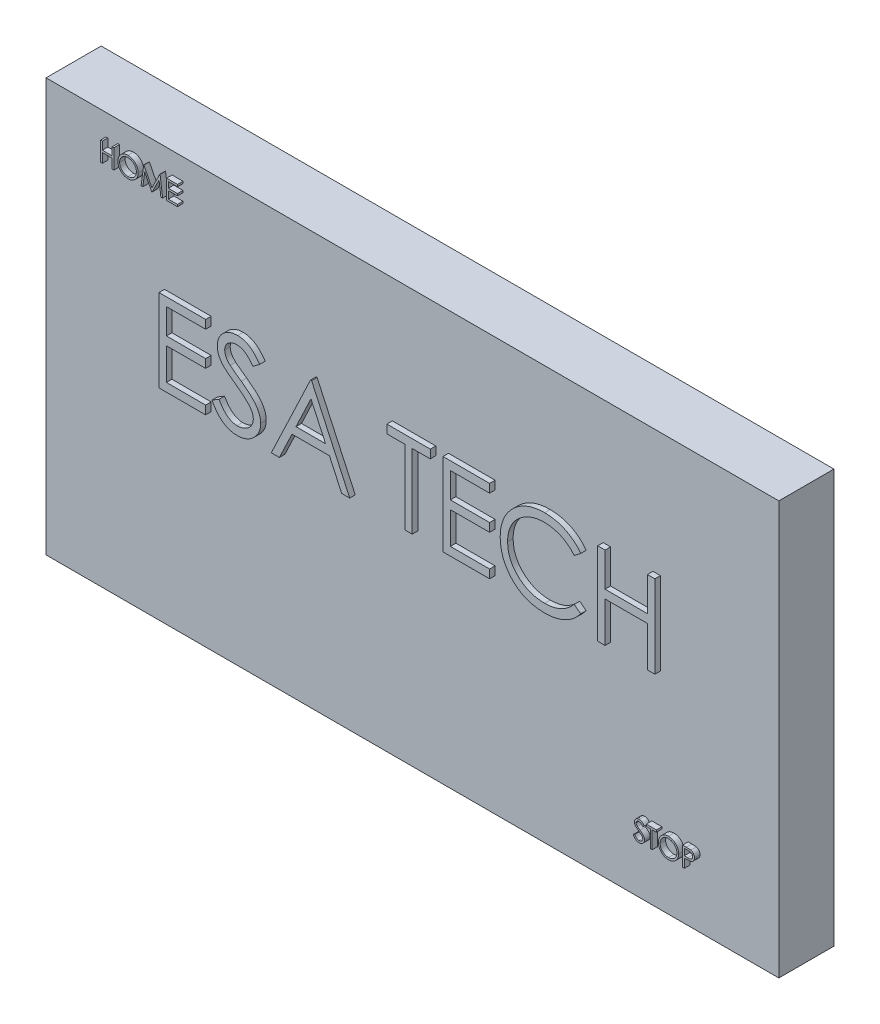
SolidWorks part; units mm, degrees
ref_plane "Front Plane" through (0, 0, 0) normal (0, 0, 1) x (1, 0, 0)
ref_plane "Top Plane" through (0, 0, 0) normal (0, 1, 0) x (1, 0, 0)
ref_plane "Right Plane" through (0, 0, 0) normal (1, 0, 0) x (0, 0, -1)
ref_plane "Plane1" through (0, 0, 10) normal (0, 0, 1) x (1, 0, 0)
sketch "Sketch1" plane through (0, 0, 10) normal (0, 0, 1) x (1, 0, 0)
  line L0 (66.5, 37.5) -> (-66.5, 37.5)
  line L1 (-66.5, 37.5) -> (-66.5, -37.5)
  line L2 (-66.5, -37.5) -> (66.5, -37.5)
  line L3 (66.5, -37.5) -> (66.5, 37.5)
extrude "Boss-Extrude1" add sketch "Sketch1" against normal blind 10
ref_plane "Plane2" through (0, 0, 13) normal (0, 0, -1) x (0, 1, 0)
sketch "Sketch2" plane through (0, 0, 13) normal (0, 0, -1) x (0, 1, 0)
  line L0 (11.9231, -27.9477) -> (12.8456, -26.7308)
  line L1 (3.6538, -34.1166) -> (2.8936, -35.3846)
  arc A0 (8.5156, -30.0721) -> (10.009, -32.0883) centre (34.1917, -12.6154) ccw
  spline S0 degree 3 poles (-0.3846, -30.8233) (-0.3828, -30.7354) (-0.3791, -30.5597) (-0.3616, -30.2964) (-0.3249, -30.0351) (-0.273, -29.7771) (-0.206, -29.5236) (-0.124, -29.2756) (-0.0267, -29.0332) (0.0861, -28.7967) (0.2147, -28.5673) (0.3586, -28.3469) (0.5159, -28.1364) (0.6848, -27.9356) (0.8638, -27.7433) (1.0538, -27.5611) (1.2539, -27.3901) (1.4634, -27.232) (1.681, -27.0864) (1.9094, -26.9577) (2.1476, -26.8461) (2.3915, -26.7477) (2.6418, -26.6696) (2.8957, -26.6115) (3.1522, -26.5662) (3.4127, -26.5437) (3.5873, -26.5402) (3.6749, -26.5385) knots 0 0 0 0 0.040239 0.080419 0.12065 0.160855 0.200779 0.240536 0.280292 0.320216 0.360325 0.400539 0.440561 0.480508 0.52052 0.560704 0.600885 0.640878 0.680723 0.720595 0.760706 0.800978 0.840861 0.880503 0.920116 0.959909 1 1 1 1
  spline S1 degree 3 poles (3.6749, -26.5385) (3.8144, -26.5452) (4.0934, -26.5588) (4.5063, -26.6299) (4.9044, -26.7529) (5.2878, -26.9125) (5.6551, -27.1073) (6.0058, -27.3308) (6.3374, -27.5804) (6.6472, -27.8548) (6.9432, -28.1442) (7.2272, -28.4464) (7.5011, -28.7582) (7.7664, -29.0775) (8.0219, -29.4047) (8.271, -29.7367) (8.4341, -29.9603) (8.5156, -30.0721) knots 0 0 0 0 0.067213 0.134445 0.201108 0.267468 0.334185 0.401073 0.467532 0.533824 0.600253 0.666833 0.733489 0.800114 0.866721 0.933348 1 1 1 1
  spline S2 degree 3 poles (10.009, -32.0883) (10.0675, -32.1477) (10.1844, -32.2663) (10.3662, -32.4375) (10.5587, -32.5955) (10.7619, -32.7375) (10.9777, -32.8593) (11.2075, -32.9565) (11.4492, -33.021) (11.6959, -33.0711) (11.8632, -33.075) (11.9471, -33.0769) knots 0 0 0 0 0.111361 0.222694 0.333843 0.444007 0.553828 0.664575 0.776591 0.888 1 1 1 1
  spline S3 degree 3 poles (11.9471, -33.0769) (12.0188, -33.0728) (12.1616, -33.0647) (12.3744, -33.0345) (12.5811, -32.9725) (12.7782, -32.8835) (12.9626, -32.77) (13.1312, -32.6343) (13.2837, -32.4803) (13.4211, -32.3123) (13.541, -32.1309) (13.6399, -31.9374) (13.7192, -31.7352) (13.7803, -31.527) (13.8207, -31.3131) (13.8388, -31.0956) (13.8437, -30.9501) (13.8462, -30.8774) knots 0 0 0 0 0.066366 0.132192 0.198089 0.265068 0.331533 0.397751 0.464609 0.531455 0.598099 0.66518 0.731934 0.798505 0.865495 0.932744 1 1 1 1
  spline S4 degree 3 poles (13.8462, -30.8774) (13.8425, -30.7829) (13.8352, -30.5941) (13.7967, -30.3139) (13.7254, -30.0416) (13.6261, -29.7791) (13.4983, -29.5287) (13.3461, -29.2923) (13.1712, -29.0731) (12.9803, -28.8684) (12.7821, -28.6704) (12.5757, -28.4802) (12.362, -28.2981) (12.1444, -28.1206) (11.9969, -28.0053) (11.9231, -27.9477) knots 0 0 0 0 0.077694 0.15521 0.231898 0.308459 0.38546 0.462477 0.539061 0.615599 0.69236 0.769264 0.846171 0.923073 1 1 1 1
  spline S5 degree 3 poles (12.8456, -26.7308) (12.9346, -26.7957) (13.1125, -26.9255) (13.3733, -27.1281) (13.6268, -27.3394) (13.8742, -27.558) (14.1129, -27.7868) (14.3397, -28.0274) (14.5511, -28.2803) (14.7436, -28.5467) (14.9107, -28.83) (15.055, -29.1268) (15.176, -29.4343) (15.2716, -29.7494) (15.3397, -30.0706) (15.3732, -30.3978) (15.3808, -30.6171) (15.3846, -30.7272) knots 0 0 0 0 0.066899 0.133692 0.200414 0.267147 0.334091 0.40104 0.467733 0.534051 0.600333 0.667098 0.734185 0.800673 0.86681 0.933166 1 1 1 1
  spline S6 degree 3 poles (15.3846, -30.7272) (15.3797, -30.8534) (15.3698, -31.1049) (15.3257, -31.4802) (15.2376, -31.8482) (15.1135, -32.2065) (14.958, -32.553) (14.7669, -32.8811) (14.5469, -33.1905) (14.2928, -33.4725) (14.0048, -33.718) (13.6951, -33.9355) (13.3607, -34.1145) (13.0074, -34.2527) (12.6414, -34.3528) (12.2648, -34.4103) (12.011, -34.4188) (11.884, -34.4231) knots 0 0 0 0 0.066708 0.132979 0.199237 0.266167 0.33303 0.399559 0.466405 0.533284 0.599492 0.665897 0.732872 0.799317 0.865884 0.932947 1 1 1 1
  spline S7 degree 3 poles (11.884, -34.4231) (11.8204, -34.4218) (11.6935, -34.4193) (11.5039, -34.4063) (11.3162, -34.3798) (11.1301, -34.3439) (10.9458, -34.2968) (10.7644, -34.2373) (10.585, -34.1702) (10.4091, -34.0939) (10.2376, -34.0085) (10.0711, -33.9137) (9.9104, -33.8096) (9.7538, -33.6993) (9.6515, -33.6229) (9.6004, -33.5847) knots 0 0 0 0 0.076926 0.153469 0.229724 0.305984 0.382514 0.459603 0.536847 0.614055 0.691256 0.768476 0.845618 0.922773 1 1 1 1
  spline S8 degree 3 poles (9.6004, -33.5847) (9.5262, -33.5219) (9.378, -33.3966) (9.1741, -33.1886) (8.9816, -32.9707) (8.7931, -32.749) (8.6088, -32.5235) (8.4282, -32.2952) (8.25, -32.0649) (8.0738, -31.8331) (7.8999, -31.5997) (7.7291, -31.3638) (7.6164, -31.2058) (7.5601, -31.1268) knots 0 0 0 0 0.09103 0.18176 0.272565 0.363469 0.454414 0.545345 0.636277 0.727213 0.818142 0.909068 1 1 1 1
  spline S9 degree 3 poles (7.5601, -31.1268) (7.4959, -31.0377) (7.3675, -30.8595) (7.173, -30.5936) (6.9749, -30.3304) (6.7708, -30.0717) (6.5621, -29.8167) (6.3506, -29.564) (6.131, -29.3184) (5.9047, -29.079) (5.6727, -28.8453) (5.4275, -28.6254) (5.2547, -28.4902) (5.1683, -28.4225) knots 0 0 0 0 0.090938 0.181862 0.272772 0.363703 0.45466 0.545612 0.636551 0.727489 0.818361 0.909111 1 1 1 1
  spline S10 degree 3 poles (5.1683, -28.4225) (5.1194, -28.3889) (5.0217, -28.3218) (4.8724, -28.2255) (4.7177, -28.1389) (4.5576, -28.0641) (4.3931, -28.0003) (4.224, -27.9481) (4.0502, -27.9116) (3.8733, -27.8936) (3.7551, -27.8876) (3.6959, -27.8846) knots 0 0 0 0 0.111507 0.22298 0.334207 0.44472 0.555086 0.665888 0.777233 0.888561 1 1 1 1
  spline S11 degree 3 poles (3.6959, -27.8846) (3.6191, -27.8881) (3.4655, -27.8951) (3.2372, -27.9251) (3.0151, -27.982) (2.8016, -28.0627) (2.5955, -28.1605) (2.3983, -28.2756) (2.2133, -28.4092) (2.0431, -28.5609) (1.8874, -28.7275) (1.7462, -28.9063) (1.6216, -29.0963) (1.5125, -29.2954) (1.4162, -29.5014) (1.334, -29.7134) (1.2679, -29.9299) (1.216, -30.1492) (1.1786, -30.3714) (1.1608, -30.5968) (1.1562, -30.7477) (1.1538, -30.8233) knots 0 0 0 0 0.05336 0.106716 0.159596 0.212162 0.264915 0.317818 0.370507 0.423067 0.475876 0.528635 0.581053 0.633442 0.686139 0.738839 0.791152 0.843193 0.895193 0.947443 1 1 1 1
  spline S12 degree 3 poles (1.1538, -30.8233) (1.1581, -30.9091) (1.1667, -31.08) (1.1964, -31.3343) (1.257, -31.582) (1.3409, -31.8228) (1.4454, -32.0567) (1.5697, -32.2811) (1.7113, -32.4945) (1.8671, -32.6974) (2.0355, -32.8906) (2.2146, -33.0736) (2.4026, -33.2465) (2.5974, -33.41) (2.7984, -33.5652) (3.0053, -33.7125) (3.2179, -33.8522) (3.4349, -33.9858) (3.5808, -34.073) (3.6538, -34.1166) knots 0 0 0 0 0.059418 0.11829 0.1767 0.235298 0.294403 0.353613 0.412465 0.471315 0.530402 0.58952 0.648316 0.706869 0.765349 0.823851 0.882453 0.941186 1 1 1 1
  spline S13 degree 3 poles (2.8936, -35.3846) (2.811, -35.3389) (2.6459, -35.2474) (2.4007, -35.1064) (2.1603, -34.9584) (1.9244, -34.8041) (1.6939, -34.6421) (1.4697, -34.4715) (1.2513, -34.2923) (1.041, -34.1022) (0.8393, -33.9016) (0.6485, -33.6911) (0.4716, -33.4703) (0.3119, -33.238) (0.167, -32.996) (0.0365, -32.7445) (-0.0774, -32.4839) (-0.1729, -32.2161) (-0.2536, -31.9448) (-0.3124, -31.6687) (-0.3532, -31.3896) (-0.3794, -31.1075) (-0.3829, -30.9183) (-0.3846, -30.8233) knots 0 0 0 0 0.047707 0.095333 0.14285 0.190289 0.237688 0.285104 0.332606 0.380306 0.428278 0.476202 0.523747 0.571081 0.618449 0.666124 0.714108 0.762015 0.809619 0.857012 0.904428 0.952035 1 1 1 1
extrude "Boss-Extrude2" add sketch "Sketch2" against normal blind 1 from surface starting at face at (0, 0, 10)
sketch "Sketch3" plane through (0, 0, 13) normal (0, 0, -1) x (0, 1, 0)
  line L0 (-25.0537, 42.7936) -> (-24.8385, 43.0775)
  line L1 (-26.9832, 41.3542) -> (-27.1606, 41.0583)
  arc A0 (-25.8488, 42.2979) -> (-25.5004, 41.8274) centre (-19.8579, 46.371) ccw
  spline S0 degree 3 poles (-27.9255, 42.1226) (-27.9244, 42.162) (-27.922, 42.2407) (-27.9033, 42.3575) (-27.8712, 42.4707) (-27.8257, 42.5791) (-27.7666, 42.6809) (-27.6961, 42.7754) (-27.6158, 42.8618) (-27.5267, 42.939) (-27.429, 43.0052) (-27.3231, 43.0577) (-27.2116, 43.0956) (-27.0957, 43.1179) (-27.0175, 43.1209) (-26.9783, 43.1224) knots 0 0 0 0 0.07724 0.154449 0.231266 0.307693 0.384533 0.461595 0.538546 0.615563 0.69251 0.769486 0.846626 0.92312 1 1 1 1
  spline S1 degree 3 poles (-26.9783, 43.1224) (-26.924, 43.1192) (-26.8157, 43.1127) (-26.6601, 43.063) (-26.5146, 42.9918) (-26.3807, 42.901) (-26.2602, 42.7938) (-26.1484, 42.6781) (-26.0438, 42.5555) (-25.9443, 42.4282) (-25.8807, 42.3413) (-25.8488, 42.2979) knots 0 0 0 0 0.111918 0.223325 0.334249 0.445556 0.556142 0.666668 0.777562 0.888771 1 1 1 1
  spline S2 degree 3 poles (-25.5004, 41.8274) (-25.4755, 41.8026) (-25.426, 41.7531) (-25.3447, 41.6867) (-25.2533, 41.6353) (-25.1527, 41.6041) (-25.0831, 41.5992) (-25.0481, 41.5968) knots 0 0 0 0 0.20138 0.401519 0.60056 0.799519 1 1 1 1
  spline S3 degree 3 poles (-25.0481, 41.5968) (-25.025, 41.598) (-24.9789, 41.6006) (-24.9111, 41.616) (-24.8478, 41.6443) (-24.7904, 41.6831) (-24.7402, 41.7306) (-24.6967, 41.7843) (-24.6616, 41.8439) (-24.6347, 41.9073) (-24.6167, 41.9736) (-24.6079, 42.0415) (-24.606, 42.0871) (-24.605, 42.11) knots 0 0 0 0 0.091854 0.182553 0.273998 0.364976 0.455736 0.546908 0.638052 0.728993 0.819242 0.909311 1 1 1 1
  spline S4 degree 3 poles (-24.605, 42.11) (-24.606, 42.1359) (-24.608, 42.1874) (-24.6211, 42.2638) (-24.6441, 42.3378) (-24.6765, 42.4084) (-24.7173, 42.4744) (-24.7656, 42.535) (-24.8184, 42.5916) (-24.8745, 42.6452) (-24.9328, 42.6964) (-24.9926, 42.7458) (-25.0334, 42.7776) (-25.0537, 42.7936) knots 0 0 0 0 0.091194 0.181497 0.272126 0.363261 0.454284 0.544761 0.635644 0.726818 0.817861 0.908901 1 1 1 1
  spline S5 degree 3 poles (-24.8385, 43.0775) (-24.8127, 43.0585) (-24.761, 43.0204) (-24.6857, 42.9605) (-24.6127, 42.8978) (-24.543, 42.8319) (-24.4779, 42.762) (-24.4183, 42.6876) (-24.3663, 42.607) (-24.3232, 42.5208) (-24.2888, 42.4308) (-24.2632, 42.3379) (-24.2493, 42.2421) (-24.2471, 42.1775) (-24.246, 42.145) knots 0 0 0 0 0.083486 0.166924 0.250412 0.333679 0.416351 0.498737 0.581477 0.665381 0.748876 0.831898 0.91544 1 1 1 1
  spline S6 degree 3 poles (-24.246, 42.145) (-24.2472, 42.1155) (-24.2495, 42.0565) (-24.2599, 41.9684) (-24.2807, 41.8823) (-24.3097, 41.7988) (-24.3461, 41.7184) (-24.3901, 41.6418) (-24.4417, 41.57) (-24.5011, 41.5042) (-24.5684, 41.4468) (-24.6408, 41.3961) (-24.7188, 41.3544) (-24.8013, 41.3223) (-24.8867, 41.2988) (-24.9745, 41.2861) (-25.0333, 41.2838) (-25.0629, 41.2827) knots 0 0 0 0 0.066883 0.133718 0.200474 0.266954 0.333497 0.400102 0.466656 0.533261 0.600199 0.666562 0.732911 0.799876 0.866694 0.933126 1 1 1 1
  spline S7 degree 3 poles (-25.0629, 41.2827) (-25.0844, 41.2833) (-25.1274, 41.2846) (-25.1916, 41.2915) (-25.2546, 41.3046) (-25.3161, 41.3229) (-25.376, 41.3453) (-25.4342, 41.3722) (-25.4903, 41.4037) (-25.5439, 41.4397) (-25.5784, 41.4654) (-25.5957, 41.4783) knots 0 0 0 0 0.111519 0.222932 0.334332 0.444896 0.555108 0.665572 0.776922 0.888442 1 1 1 1
  spline S8 degree 3 poles (-25.5957, 41.4783) (-25.6325, 41.5119) (-25.7061, 41.579) (-25.802, 41.6939) (-25.8945, 41.811) (-25.9845, 41.9304) (-26.0427, 42.0113) (-26.0718, 42.0518) knots 0 0 0 0 0.200006 0.399688 0.599775 0.799884 1 1 1 1
  spline S9 degree 3 poles (-26.0718, 42.0518) (-26.0954, 42.0844) (-26.1427, 42.1496) (-26.2155, 42.2459) (-26.2905, 42.3407) (-26.368, 42.4334) (-26.45, 42.5221) (-26.5358, 42.6071) (-26.5985, 42.6576) (-26.6299, 42.6828) knots 0 0 0 0 0.142925 0.285812 0.42871 0.57166 0.714555 0.857318 1 1 1 1
  spline S10 degree 3 poles (-26.6299, 42.6828) (-26.6446, 42.6928) (-26.674, 42.7127) (-26.7195, 42.7402) (-26.7668, 42.7643) (-26.8162, 42.7835) (-26.8673, 42.7982) (-26.9201, 42.8057) (-26.9556, 42.8074) (-26.9734, 42.8083) knots 0 0 0 0 0.143345 0.286448 0.428817 0.570734 0.71309 0.856546 1 1 1 1
  spline S11 degree 3 poles (-26.9734, 42.8083) (-26.9996, 42.8069) (-27.0519, 42.8042) (-27.1287, 42.788) (-27.2011, 42.7591) (-27.2696, 42.7223) (-27.3321, 42.6757) (-27.388, 42.6214) (-27.4362, 42.5603) (-27.4766, 42.4939) (-27.5095, 42.4237) (-27.535, 42.3508) (-27.5536, 42.2761) (-27.5643, 42.1997) (-27.5658, 42.1484) (-27.5666, 42.1226) knots 0 0 0 0 0.07813 0.155514 0.232377 0.309483 0.386489 0.463562 0.54069 0.617593 0.694391 0.771031 0.847162 0.923259 1 1 1 1
  spline S12 degree 3 poles (-27.5666, 42.1226) (-27.5652, 42.0945) (-27.5625, 42.0384) (-27.5465, 41.9553) (-27.5182, 41.8756) (-27.4805, 41.7997) (-27.4344, 41.7287) (-27.3817, 41.6625) (-27.3236, 41.6012) (-27.2614, 41.5446) (-27.1958, 41.492) (-27.127, 41.4432) (-27.0558, 41.3977) (-27.0074, 41.3687) (-26.9832, 41.3542) knots 0 0 0 0 0.083395 0.166197 0.249846 0.333369 0.416608 0.500374 0.583715 0.666634 0.749555 0.83277 0.916365 1 1 1 1
  spline S13 degree 3 poles (-27.1606, 41.0583) (-27.2056, 41.0836) (-27.2954, 41.134) (-27.4249, 41.218) (-27.5465, 41.3129) (-27.658, 41.4194) (-27.7546, 41.5397) (-27.8309, 41.674) (-27.8859, 41.8179) (-27.9181, 41.969) (-27.9231, 42.0713) (-27.9255, 42.1226) knots 0 0 0 0 0.11174 0.223059 0.334051 0.445242 0.55645 0.667007 0.778285 0.888942 1 1 1 1
extrude "Boss-Extrude3" add sketch "Sketch3" against normal blind 1 from surface starting at face at (-30.8018, 7.7955, 10)
sketch "Sketch4" plane through (0, 0, 10) normal (0, 0, 1) x (1, 0, 0)
  line L0 (-55.6069, 30.1611) -> (-55.6069, 33.6611)
  line L1 (-55.6069, 33.6611) -> (-55.2928, 33.6611)
  line L2 (-55.2928, 33.6611) -> (-55.2928, 32.2252)
  line L3 (-55.2928, 32.2252) -> (-53.4979, 32.2252)
  line L4 (-53.4979, 32.2252) -> (-53.4979, 33.6611)
  line L5 (-53.4979, 33.6611) -> (-53.1838, 33.6611)
  line L6 (-53.1838, 33.6611) -> (-53.1838, 30.1611)
  line L7 (-53.1838, 30.1611) -> (-53.4979, 30.1611)
  line L8 (-53.4979, 30.1611) -> (-53.4979, 31.8663)
  line L9 (-53.4979, 31.8663) -> (-55.2928, 31.8663)
  line L10 (-55.2928, 31.8663) -> (-55.2928, 30.1611)
  line L11 (-55.2928, 30.1611) -> (-55.6069, 30.1611)
extrude "Boss-Extrude4" add sketch "Sketch4" along normal blind 1
sketch "Sketch5" plane through (0, 0, 10) normal (0, 0, 1) x (1, 0, 0)
  line L0 (34.6154, 0) -> (34.6154, 15)
  line L1 (34.6154, 15) -> (35.9615, 15)
  line L2 (35.9615, 15) -> (35.9615, 8.8462)
  line L3 (35.9615, 8.8462) -> (43.6538, 8.8462)
  line L4 (43.6538, 8.8462) -> (43.6538, 15)
  line L5 (43.6538, 15) -> (45, 15)
  line L6 (45, 15) -> (45, 0)
  line L7 (45, 0) -> (43.6538, 0)
  line L8 (43.6538, 0) -> (43.6538, 7.3077)
  line L9 (43.6538, 7.3077) -> (35.9615, 7.3077)
  line L10 (35.9615, 7.3077) -> (35.9615, 0)
  line L11 (35.9615, 0) -> (34.6154, 0)
extrude "Boss-Extrude5" add sketch "Sketch5" along normal blind 1
sketch "Sketch6" plane through (0, 0, 10) normal (0, 0, 1) x (1, 0, 0)
  line L0 (6.5385, 0) -> (6.5385, 15)
  line L1 (6.5385, 15) -> (15, 15)
  line L2 (15, 15) -> (15, 13.4615)
  line L3 (15, 13.4615) -> (7.8846, 13.4615)
  line L4 (7.8846, 13.4615) -> (7.8846, 8.8462)
  line L5 (7.8846, 8.8462) -> (15, 8.8462)
  line L6 (15, 8.8462) -> (15, 7.3077)
  line L7 (15, 7.3077) -> (7.8846, 7.3077)
  line L8 (7.8846, 7.3077) -> (7.8846, 1.5385)
  line L9 (7.8846, 1.5385) -> (15, 1.5385)
  line L10 (15, 1.5385) -> (15, 0)
  line L11 (15, 0) -> (6.5385, 0)
extrude "Boss-Extrude6" add sketch "Sketch6" along normal blind 1
sketch "Sketch7" plane through (0, 0, 10) normal (0, 0, 1) x (1, 0, 0)
  line L0 (-45, 0) -> (-45, 15)
  line L1 (-45, 15) -> (-36.5385, 15)
  line L2 (-36.5385, 15) -> (-36.5385, 13.4615)
  line L3 (-36.5385, 13.4615) -> (-43.6538, 13.4615)
  line L4 (-43.6538, 13.4615) -> (-43.6538, 8.8462)
  line L5 (-43.6538, 8.8462) -> (-36.5385, 8.8462)
  line L6 (-36.5385, 8.8462) -> (-36.5385, 7.3077)
  line L7 (-36.5385, 7.3077) -> (-43.6538, 7.3077)
  line L8 (-43.6538, 7.3077) -> (-43.6538, 1.5385)
  line L9 (-43.6538, 1.5385) -> (-36.5385, 1.5385)
  line L10 (-36.5385, 1.5385) -> (-36.5385, 0)
  line L11 (-36.5385, 0) -> (-45, 0)
extrude "Boss-Extrude7" add sketch "Sketch7" along normal blind 1
sketch "Sketch8" plane through (0, 0, 10) normal (0, 0, 1) x (1, 0, 0)
  line L0 (-47.9317, 30.1611) -> (-48.2479, 30.1611)
  line L1 (-48.2479, 30.1611) -> (-47.7859, 33.6611)
  line L2 (-47.7859, 33.6611) -> (-47.741, 33.6611)
  line L3 (-47.741, 33.6611) -> (-46.296, 30.7893)
  line L4 (-46.296, 30.7893) -> (-44.8545, 33.6611)
  line L5 (-44.8545, 33.6611) -> (-44.8089, 33.6611)
  line L6 (-44.8089, 33.6611) -> (-44.3441, 30.1611)
  line L7 (-44.3441, 30.1611) -> (-44.6596, 30.1611)
  line L8 (-44.6596, 30.1611) -> (-44.9947, 32.6796)
  line L9 (-44.9947, 32.6796) -> (-46.2935, 30.0906)
  line L10 (-46.2935, 30.0906) -> (-47.5973, 32.6852)
  line L11 (-47.5973, 32.6852) -> (-47.9317, 30.1611)
extrude "Boss-Extrude8" add sketch "Sketch8" along normal blind 1
sketch "Sketch9" plane through (0, 0, 10) normal (0, 0, 1) x (1, 0, 0)
  line L0 (-43.6261, 30.1611) -> (-43.6261, 33.6611)
  line L1 (-43.6261, 33.6611) -> (-41.6517, 33.6611)
  line L2 (-41.6517, 33.6611) -> (-41.6517, 33.3022)
  line L3 (-41.6517, 33.3022) -> (-43.312, 33.3022)
  line L4 (-43.312, 33.3022) -> (-43.312, 32.2252)
  line L5 (-43.312, 32.2252) -> (-41.6517, 32.2252)
  line L6 (-41.6517, 32.2252) -> (-41.6517, 31.8663)
  line L7 (-41.6517, 31.8663) -> (-43.312, 31.8663)
  line L8 (-43.312, 31.8663) -> (-43.312, 30.5201)
  line L9 (-43.312, 30.5201) -> (-41.6517, 30.5201)
  line L10 (-41.6517, 30.5201) -> (-41.6517, 30.1611)
  line L11 (-41.6517, 30.1611) -> (-43.6261, 30.1611)
extrude "Boss-Extrude9" add sketch "Sketch9" along normal blind 1
sketch "Sketch10" plane through (0, 0, 13) normal (0, 0, -1) x (0, 1, 0)
  line L0 (2.7614, 31.5385) -> (3.6538, 30.3606)
  line L1 (11.3462, 30.3606) -> (12.2476, 31.5385)
  spline S0 degree 3 poles (15.3846, 24.994) (15.3778, 24.715) (15.3643, 24.159) (15.2559, 23.3312) (15.0732, 22.5158) (14.8021, 21.7242) (14.4444, 20.9701) (14.0123, 20.2583) (13.4974, 19.6006) (12.9207, 18.9944) (12.2856, 18.4482) (11.5951, 17.9728) (10.8531, 17.5828) (10.0721, 17.28) (9.2613, 17.0707) (8.4296, 16.9445) (7.8681, 16.9302) (7.5871, 16.9231) knots 0 0 0 0 0.066758 0.133076 0.199482 0.266503 0.332902 0.398939 0.46541 0.532434 0.598956 0.665577 0.732677 0.799148 0.86564 0.932775 1 1 1 1
  spline S1 degree 3 poles (7.5871, 16.9231) (7.3715, 16.9274) (6.9405, 16.9361) (6.2966, 17.002) (5.6615, 17.1142) (5.0386, 17.2725) (4.4327, 17.4824) (3.8447, 17.744) (3.2796, 18.0566) (2.7403, 18.4161) (2.4059, 18.6887) (2.2386, 18.8251) knots 0 0 0 0 0.111471 0.22287 0.334239 0.444703 0.554834 0.665414 0.77702 0.88843 1 1 1 1
  spline S2 degree 3 poles (2.2386, 18.8251) (2.1554, 18.8984) (1.9896, 19.0446) (1.7525, 19.2758) (1.5283, 19.5178) (1.3136, 19.7678) (1.1108, 20.0281) (0.9209, 20.2992) (0.7423, 20.5789) (0.576, 20.866) (0.4242, 21.1598) (0.2874, 21.4595) (0.1641, 21.7643) (0.0552, 22.0745) (-0.0422, 22.389) (-0.1277, 22.7083) (-0.1977, 23.0325) (-0.257, 23.3592) (-0.3043, 23.6878) (-0.3402, 24.0174) (-0.368, 24.3479) (-0.3826, 24.6797) (-0.3839, 24.9012) (-0.3846, 25.012) knots 0 0 0 0 0.04786 0.09548 0.142932 0.19033 0.237762 0.285388 0.333232 0.381057 0.428636 0.476012 0.523294 0.570581 0.617947 0.665499 0.713281 0.761133 0.808901 0.856621 0.90434 0.952119 1 1 1 1
  spline S3 degree 3 poles (-0.3846, 25.012) (-0.3781, 25.2922) (-0.3651, 25.8522) (-0.2534, 26.6865) (-0.0595, 27.5025) (0.2145, 28.2938) (0.5763, 29.0491) (1.0127, 29.7632) (1.5291, 30.4189) (2.1072, 31.0203) (2.5427, 31.3652) (2.7614, 31.5385) knots 0 0 0 0 0.111698 0.223272 0.334921 0.445652 0.556564 0.668254 0.778683 0.888841 1 1 1 1
  spline S4 degree 3 poles (3.6538, 30.3606) (3.5651, 30.2797) (3.3877, 30.1181) (3.1277, 29.8698) (2.8808, 29.6089) (2.6482, 29.3352) (2.4293, 29.0493) (2.2249, 28.7522) (2.0365, 28.4453) (1.8652, 28.1297) (1.7122, 27.8056) (1.5779, 27.4727) (1.4619, 27.1318) (1.3645, 26.7846) (1.2852, 26.4332) (1.2241, 26.079) (1.1836, 25.7221) (1.1638, 25.363) (1.1572, 25.1231) (1.1538, 25.003) knots 0 0 0 0 0.058939 0.117759 0.176444 0.235131 0.294023 0.353112 0.412039 0.470701 0.529256 0.587892 0.646789 0.705904 0.764832 0.823527 0.882202 0.941028 1 1 1 1
  spline S5 degree 3 poles (1.1538, 25.003) (1.1581, 24.773) (1.1665, 24.3145) (1.2546, 23.6321) (1.3979, 22.9589) (1.6088, 22.3018) (1.8905, 21.6719) (2.2366, 21.0749) (2.6494, 20.5214) (3.1142, 20.0106) (3.6304, 19.552) (4.1924, 19.1502) (4.7998, 18.8229) (5.439, 18.5658) (6.1068, 18.3938) (6.7915, 18.2869) (7.2538, 18.2751) (7.485, 18.2692) knots 0 0 0 0 0.06675 0.133041 0.199383 0.266333 0.332972 0.399343 0.466238 0.53306 0.599504 0.666333 0.733147 0.799339 0.865844 0.932938 1 1 1 1
  spline S6 degree 3 poles (7.485, 18.2692) (7.5893, 18.2707) (7.7977, 18.2736) (8.1095, 18.2922) (8.419, 18.3288) (8.727, 18.3774) (9.0329, 18.4415) (9.3354, 18.521) (9.6326, 18.6163) (9.9225, 18.728) (10.2067, 18.8515) (10.4839, 18.99) (10.7525, 19.1459) (11.0142, 19.3154) (11.2685, 19.4964) (11.5125, 19.6896) (11.7439, 19.8953) (11.963, 20.1126) (12.1711, 20.3401) (12.3685, 20.5779) (12.5552, 20.8259) (12.7309, 21.0831) (12.8947, 21.3482) (13.0451, 21.6204) (13.1829, 21.8982) (13.3115, 22.1803) (13.4257, 22.4693) (13.5247, 22.7648) (13.6114, 23.0644) (13.6857, 23.367) (13.7448, 23.6721) (13.7898, 23.979) (13.8244, 24.2875) (13.8419, 24.5982) (13.8447, 24.8058) (13.8462, 24.9099) knots 0 0 0 0 0.030521 0.060934 0.09128 0.121635 0.152096 0.182641 0.213063 0.243309 0.273474 0.303628 0.333867 0.364264 0.394779 0.425106 0.455238 0.485273 0.5153 0.545388 0.575618 0.606034 0.636441 0.666721 0.69693 0.727125 0.757366 0.78775 0.81821 0.848574 0.878828 0.909041 0.939267 0.969576 1 1 1 1
  spline S7 degree 3 poles (13.8462, 24.9099) (13.8406, 25.1407) (13.8296, 25.6021) (13.7406, 26.2898) (13.5881, 26.9638) (13.3716, 27.6184) (13.0893, 28.2476) (12.7423, 28.8445) (12.3358, 29.4024) (11.869, 29.9111) (11.5208, 30.2104) (11.3462, 30.3606) knots 0 0 0 0 0.111549 0.222977 0.334512 0.445081 0.555665 0.667244 0.778199 0.888721 1 1 1 1
  spline S8 degree 3 poles (12.2476, 31.5385) (12.3351, 31.4722) (12.5097, 31.3399) (12.7639, 31.1329) (13.0056, 30.9136) (13.2343, 30.6825) (13.4549, 30.4439) (13.6642, 30.1949) (13.8619, 29.9352) (14.0489, 29.6658) (14.225, 29.3878) (14.3893, 29.1025) (14.5411, 28.8114) (14.68, 28.515) (14.8057, 28.2135) (14.9194, 27.9072) (15.0221, 27.5963) (15.1099, 27.2796) (15.1846, 26.9585) (15.2474, 26.6346) (15.2992, 26.3089) (15.3391, 25.982) (15.3671, 25.6537) (15.3808, 25.3241) (15.3833, 25.1041) (15.3846, 24.994) knots 0 0 0 0 0.043674 0.087128 0.130334 0.173403 0.216441 0.259526 0.302756 0.34621 0.38993 0.433609 0.477131 0.520478 0.56375 0.607032 0.650401 0.693961 0.737695 0.781492 0.82519 0.868833 0.912478 0.956195 1 1 1 1
extrude "Boss-Extrude10" add sketch "Sketch10" against normal blind 1 from surface starting at face at (42.1276, -26.0168, 10)
sketch "Sketch11" plane through (0, 0, 10) normal (0, 0, 1) x (1, 0, 0)
  line L0 (-0.3846, 13.4615) -> (-3.6538, 13.4615)
  line L1 (-3.6538, 13.4615) -> (-3.6538, 15)
  line L2 (-3.6538, 15) -> (4.2308, 15)
  line L3 (4.2308, 15) -> (4.2308, 13.4615)
  line L4 (4.2308, 13.4615) -> (0.9615, 13.4615)
  line L5 (0.9615, 13.4615) -> (0.9615, 0)
  line L6 (0.9615, 0) -> (-0.3846, 0)
  line L7 (-0.3846, 0) -> (-0.3846, 13.4615)
extrude "Boss-Extrude11" add sketch "Sketch11" along normal blind 1
sketch "Sketch12" plane through (0, 0, 10) normal (0, 0, 1) x (1, 0, 0)
  line L0 (44.1993, -24.6948) -> (43.4365, -24.6948)
  line L1 (43.4365, -24.6948) -> (43.4365, -24.3358)
  line L2 (43.4365, -24.3358) -> (45.2762, -24.3358)
  line L3 (45.2762, -24.3358) -> (45.2762, -24.6948)
  line L4 (45.2762, -24.6948) -> (44.5134, -24.6948)
  line L5 (44.5134, -24.6948) -> (44.5134, -27.8358)
  line L6 (44.5134, -27.8358) -> (44.1993, -27.8358)
  line L7 (44.1993, -27.8358) -> (44.1993, -24.6948)
extrude "Boss-Extrude12" add sketch "Sketch12" along normal blind 1
sketch "Sketch13" plane through (0, 0, 13) normal (0, 0, -1) x (0, 1, 0)
  line L0 (-27.8358, 50.0327) -> (-27.8358, 50.3468)
  line L1 (-27.8358, 50.3468) -> (-26.2204, 50.3468)
  line L2 (-26.2204, 50.3468) -> (-26.2204, 50.5971)
  line L3 (-24.3358, 50.7191) -> (-24.3358, 50.0327)
  line L4 (-24.3358, 50.0327) -> (-27.8358, 50.0327)
  arc A0 (-26.2204, 50.5971) -> (-26.1629, 51.4882) centre (-21.72, 50.7541) cw
  spline S0 degree 3 poles (-26.1629, 51.4882) (-26.1502, 51.5321) (-26.1248, 51.6199) (-26.0696, 51.746) (-25.9956, 51.8621) (-25.903, 51.964) (-25.7953, 52.0495) (-25.6743, 52.1144) (-25.545, 52.1587) (-25.4105, 52.1818) (-25.32, 52.1849) (-25.2746, 52.1865) knots 0 0 0 0 0.111507 0.222806 0.334641 0.445778 0.5572 0.668421 0.779236 0.889271 1 1 1 1
  spline S1 degree 3 poles (-25.2746, 52.1865) (-25.2378, 52.1856) (-25.1643, 52.1839) (-25.0552, 52.1673) (-24.9483, 52.1404) (-24.8464, 52.0987) (-24.7511, 52.044) (-24.6646, 51.9765) (-24.5866, 51.8996) (-24.5185, 51.8141) (-24.4627, 51.7205) (-24.4194, 51.6206) (-24.3987, 51.5511) (-24.3884, 51.5162) knots 0 0 0 0 0.091605 0.183215 0.274495 0.365703 0.456832 0.54753 0.638507 0.729334 0.819445 0.909305 1 1 1 1
  spline S2 degree 3 poles (-24.3884, 51.5162) (-24.3782, 51.4638) (-24.358, 51.359) (-24.3475, 51.1991) (-24.3402, 51.0393) (-24.3365, 50.8792) (-24.336, 50.7724) (-24.3358, 50.7191) knots 0 0 0 0 0.200017 0.399771 0.599836 0.799914 1 1 1 1
extrude "Boss-Extrude13" add sketch "Sketch13" against normal blind 1 from surface starting at face at (25.2486, 6.9475, 10)
ref_plane "Plane3" through (0, 0, 8) normal (0, 0, 1) x (1, 0, 0)
sketch "Sketch14" plane through (0, 0, 8) normal (0, 0, 1) x (1, 0, 0)
  line L0 (50.9595, -25.8691) -> (50.3468, -25.8614)
  line L1 (50.3468, -25.8614) -> (50.3468, -24.6948)
  line L2 (50.3468, -24.6948) -> (50.9869, -24.6948)
  spline S0 degree 3 poles (50.9869, -24.6948) (51.0233, -24.695) (51.0959, -24.6955) (51.2048, -24.7003) (51.3135, -24.7105) (51.4216, -24.7272) (51.5273, -24.757) (51.6254, -24.8075) (51.7102, -24.8781) (51.7801, -24.9634) (51.8333, -25.0601) (51.8661, -25.166) (51.8703, -25.2393) (51.8724, -25.276) knots 0 0 0 0 0.090673 0.181128 0.2715 0.36262 0.453423 0.544063 0.635183 0.726565 0.81743 0.908708 1 1 1 1
  spline S1 degree 3 poles (51.8724, -25.276) (51.8707, -25.3077) (51.8674, -25.3709) (51.8447, -25.4639) (51.8054, -25.5509) (51.752, -25.6301) (51.687, -25.7001) (51.6097, -25.7565) (51.5244, -25.7996) (51.4332, -25.8283) (51.3396, -25.8463) (51.245, -25.8577) (51.15, -25.865) (51.0548, -25.8687) (50.9913, -25.869) (50.9595, -25.8691) knots 0 0 0 0 0.076797 0.153354 0.230466 0.307229 0.384293 0.460869 0.538052 0.614923 0.692002 0.769061 0.845964 0.922924 1 1 1 1
extrude "Cut-Extrude1" cut sketch "Sketch14" against normal blind 1 from surface starting at face at (50.7647, -25.7465, 11)
sketch "Sketch15" plane through (0, 0, 13) normal (0, 0, -1) x (0, 1, 0)
  spline S0 degree 3 poles (-26.1012, 45.6352) (-26.1656, 45.6369) (-26.2938, 45.6402) (-26.4843, 45.6693) (-26.6711, 45.717) (-26.8511, 45.7864) (-27.022, 45.8753) (-27.1823, 45.9821) (-27.3304, 46.1058) (-27.466, 46.2434) (-27.588, 46.3932) (-27.6936, 46.555) (-27.7805, 46.7271) (-27.8469, 46.9077) (-27.8925, 47.095) (-27.9207, 47.2867) (-27.9239, 47.416) (-27.9255, 47.4806) knots 0 0 0 0 0.066774 0.133078 0.199613 0.26661 0.332929 0.399236 0.4662 0.532927 0.599494 0.666524 0.73309 0.799259 0.865865 0.932947 1 1 1 1
  spline S1 degree 3 poles (-27.9255, 47.4806) (-27.9239, 47.5451) (-27.9207, 47.6736) (-27.8923, 47.8646) (-27.8452, 48.052) (-27.777, 48.2329) (-27.6887, 48.4045) (-27.5819, 48.565) (-27.4587, 48.7139) (-27.3215, 48.8502) (-27.1719, 48.9731) (-27.0104, 49.0795) (-26.8384, 49.1673) (-26.6578, 49.2345) (-26.4705, 49.2811) (-26.2785, 49.3098) (-26.1491, 49.3131) (-26.0844, 49.3147) knots 0 0 0 0 0.066811 0.133161 0.199726 0.266757 0.333073 0.399352 0.466281 0.533023 0.599575 0.666576 0.733164 0.799321 0.865881 0.932956 1 1 1 1
  spline S2 degree 3 poles (-26.0844, 49.3147) (-26.0266, 49.3133) (-25.9111, 49.3106) (-25.7395, 49.2887) (-25.5714, 49.252) (-25.4076, 49.1992) (-25.2499, 49.1295) (-25.0997, 49.0448) (-24.9591, 48.9452) (-24.8287, 48.8327) (-24.7078, 48.7099) (-24.5984, 48.5773) (-24.5023, 48.4355) (-24.4205, 48.2846) (-24.3548, 48.1258) (-24.3049, 47.9617) (-24.2694, 47.7944) (-24.2514, 47.624) (-24.2478, 47.5098) (-24.246, 47.4525) knots 0 0 0 0 0.059398 0.118616 0.177332 0.235995 0.295058 0.354146 0.412863 0.471759 0.530912 0.589642 0.648097 0.70664 0.765653 0.824322 0.882639 0.941106 1 1 1 1
  spline S3 degree 3 poles (-24.246, 47.4525) (-24.2469, 47.4063) (-24.2485, 47.3138) (-24.2649, 47.176) (-24.2901, 47.0401) (-24.3266, 46.9074) (-24.373, 46.7781) (-24.429, 46.6524) (-24.4946, 46.531) (-24.5689, 46.4149) (-24.652, 46.3055) (-24.7432, 46.2028) (-24.8419, 46.1066) (-24.9483, 46.019) (-25.0607, 45.9399) (-25.1781, 45.8692) (-25.3004, 45.8068) (-25.4274, 45.7538) (-25.5582, 45.71) (-25.6915, 45.6761) (-25.8267, 45.6528) (-25.9634, 45.6375) (-26.0551, 45.636) (-26.1012, 45.6352) knots 0 0 0 0 0.048005 0.096009 0.143882 0.19137 0.23875 0.286347 0.334196 0.38187 0.429272 0.476716 0.524412 0.572155 0.6197 0.666978 0.714352 0.762069 0.809834 0.857394 0.904742 0.952187 1 1 1 1
extrude "Boss-Extrude14" add sketch "Sketch15" against normal blind 1 from surface starting at face at (25.2486, 6.9475, 10)
sketch "Sketch16" plane through (0, 0, 8) normal (0, 0, 1) x (1, 0, 0)
  spline S0 degree 3 poles (45.9493, -26.0998) (45.9509, -26.0471) (45.9541, -25.942) (45.977, -25.7854) (46.0169, -25.6325) (46.0735, -25.4851) (46.1467, -25.3459) (46.2333, -25.2143) (46.335, -25.0934) (46.4491, -24.9835) (46.5743, -24.8864) (46.7086, -24.8025) (46.8503, -24.7323) (46.9982, -24.6757) (47.1515, -24.6344) (47.309, -24.6105) (47.4149, -24.6069) (47.468, -24.605) knots 0 0 0 0 0.066732 0.133058 0.199814 0.266465 0.332514 0.398649 0.465449 0.532144 0.598858 0.665623 0.732286 0.798881 0.865821 0.93288 1 1 1 1
  spline S1 degree 3 poles (47.468, -24.605) (47.5206, -24.6068) (47.6257, -24.6104) (47.7823, -24.6331) (47.9353, -24.673) (48.0838, -24.7276) (48.2261, -24.7963) (48.3618, -24.8775) (48.4892, -24.9714) (48.6055, -25.079) (48.7087, -25.1987) (48.7983, -25.3289) (48.8729, -25.468) (48.9313, -25.615) (48.9721, -25.768) (48.9955, -25.9251) (48.9989, -26.0308) (49.0006, -26.0837) knots 0 0 0 0 0.066731 0.133083 0.199801 0.266661 0.333114 0.399638 0.466595 0.533191 0.599806 0.666427 0.732892 0.799341 0.866199 0.933047 1 1 1 1
  spline S2 degree 3 poles (49.0006, -26.0837) (48.9989, -26.1366) (48.9956, -26.2421) (48.9725, -26.3992) (48.9324, -26.5528) (48.8751, -26.7008) (48.8017, -26.8411) (48.714, -26.9731) (48.6117, -27.0946) (48.4955, -27.2032) (48.3687, -27.2989) (48.2328, -27.3811) (48.0893, -27.4491) (47.9394, -27.5019) (47.7849, -27.5398) (47.627, -27.5619) (47.521, -27.565) (47.468, -27.5666) knots 0 0 0 0 0.066735 0.133077 0.199829 0.266584 0.332825 0.399183 0.4661 0.532735 0.599412 0.666141 0.732763 0.799365 0.866283 0.933093 1 1 1 1
  spline S3 degree 3 poles (47.468, -27.5666) (47.4218, -27.5652) (47.3297, -27.5625) (47.1921, -27.547) (47.0567, -27.5179) (46.9243, -27.4773) (46.797, -27.4238) (46.6754, -27.3591) (46.5604, -27.2829) (46.4522, -27.1967) (46.3514, -27.1018) (46.259, -26.9989) (46.1764, -26.8877) (46.1058, -26.7683) (46.0476, -26.6428) (46.0029, -26.5121) (45.9712, -26.3773) (45.9543, -26.2391) (45.951, -26.1463) (45.9493, -26.0998) knots 0 0 0 0 0.05895 0.117597 0.176423 0.235452 0.294144 0.352468 0.410989 0.469983 0.52889 0.587516 0.646287 0.705415 0.764183 0.822635 0.881458 0.94065 1 1 1 1
extrude "Cut-Extrude2" cut sketch "Sketch16" against normal blind 1 from surface starting at face at (47.4708, -26.0893, 11)
sketch "Sketch17" plane through (0, 0, 13) normal (0, 0, -1) x (0, 1, 0)
  spline S0 degree 3 poles (31.8957, -52.4658) (31.8445, -52.4646) (31.7422, -52.4622) (31.5901, -52.4447) (31.4407, -52.4147) (31.2947, -52.3723) (31.153, -52.3165) (31.0165, -52.2481) (30.8865, -52.1684) (30.764, -52.0779) (30.6493, -51.9776) (30.5424, -51.8687) (30.4441, -51.7522) (30.3557, -51.6287) (30.2782, -51.4981) (30.2123, -51.3608) (30.1592, -51.2181) (30.1194, -51.0717) (30.0911, -50.9233) (30.0749, -50.7725) (30.0726, -50.6713) (30.0714, -50.6205) knots 0 0 0 0 0.053139 0.106173 0.15877 0.211155 0.263747 0.316654 0.369437 0.421904 0.474537 0.527508 0.580176 0.632588 0.684985 0.73766 0.790494 0.842799 0.89494 0.947257 1 1 1 1
  spline S1 degree 3 poles (30.0714, -50.6205) (30.0726, -50.5692) (30.0749, -50.4668) (30.092, -50.3143) (30.1215, -50.1644) (30.1633, -50.018) (30.2181, -49.8756) (30.2859, -49.7386) (30.3654, -49.6082) (30.4558, -49.4853) (30.5557, -49.37) (30.6642, -49.2627) (30.7802, -49.1638) (30.9034, -49.0748) (31.0339, -48.9965) (31.1712, -48.9298) (31.314, -48.876) (31.4605, -48.8353) (31.6092, -48.8064) (31.7603, -48.7899) (31.8616, -48.7876) (31.9125, -48.7864) knots 0 0 0 0 0.053111 0.106173 0.158842 0.211249 0.263802 0.316692 0.369494 0.421964 0.47455 0.527436 0.580038 0.632412 0.684802 0.737511 0.790411 0.842761 0.894923 0.947248 1 1 1 1
  spline S2 degree 3 poles (31.9125, -48.7864) (31.9704, -48.7877) (32.0859, -48.7905) (32.2574, -48.8124) (32.4256, -48.8491) (32.5893, -48.9019) (32.747, -48.9716) (32.8972, -49.0562) (33.0378, -49.1559) (33.1683, -49.2684) (33.2892, -49.3911) (33.3986, -49.5237) (33.4946, -49.6656) (33.5764, -49.8165) (33.6422, -49.9752) (33.6921, -50.1394) (33.7275, -50.3067) (33.7455, -50.477) (33.7491, -50.5912) (33.7509, -50.6485) knots 0 0 0 0 0.059398 0.118616 0.177332 0.235995 0.295058 0.354146 0.412863 0.471759 0.530912 0.589642 0.648097 0.70664 0.765653 0.824322 0.882639 0.941106 1 1 1 1
  spline S3 degree 3 poles (33.7509, -50.6485) (33.75, -50.6948) (33.7484, -50.7873) (33.732, -50.9251) (33.7068, -51.061) (33.6704, -51.1937) (33.6239, -51.3229) (33.5679, -51.4487) (33.5024, -51.5701) (33.428, -51.6861) (33.345, -51.7956) (33.2537, -51.8983) (33.1551, -51.9945) (33.0486, -52.0821) (32.9362, -52.1611) (32.8188, -52.2319) (32.6966, -52.2942) (32.5695, -52.3473) (32.4387, -52.391) (32.3054, -52.4249) (32.1702, -52.4483) (32.0336, -52.4636) (31.9418, -52.4651) (31.8957, -52.4658) knots 0 0 0 0 0.048005 0.096009 0.143882 0.19137 0.23875 0.286347 0.334196 0.38187 0.429272 0.476716 0.524412 0.572155 0.6197 0.666978 0.714352 0.762069 0.809834 0.857394 0.904742 0.952187 1 1 1 1
extrude "Boss-Extrude15" add sketch "Sketch17" against normal blind 1 from surface starting at face at (47.4708, -26.0893, 10)
sketch "Sketch18" plane through (0, 0, 8) normal (0, 0, 1) x (1, 0, 0)
  spline S0 degree 3 poles (-52.1517, 31.8971) (-52.1502, 31.9498) (-52.147, 32.0549) (-52.1241, 32.2115) (-52.0842, 32.3644) (-52.0276, 32.5118) (-51.9543, 32.6511) (-51.8677, 32.7826) (-51.766, 32.9035) (-51.652, 33.0134) (-51.5268, 33.1105) (-51.3925, 33.1944) (-51.2507, 33.2646) (-51.1028, 33.3212) (-50.9496, 33.3625) (-50.7921, 33.3864) (-50.6861, 33.3901) (-50.6331, 33.3919) knots 0 0 0 0 0.066732 0.133058 0.199814 0.266465 0.332514 0.398649 0.465449 0.532144 0.598858 0.665623 0.732286 0.798881 0.865821 0.93288 1 1 1 1
  spline S1 degree 3 poles (-50.6331, 33.3919) (-50.5804, 33.3901) (-50.4753, 33.3865) (-50.3188, 33.3638) (-50.1658, 33.3239) (-50.0173, 33.2693) (-49.875, 33.2006) (-49.7393, 33.1195) (-49.6119, 33.0256) (-49.4956, 32.918) (-49.3923, 32.7982) (-49.3028, 32.668) (-49.2282, 32.5289) (-49.1698, 32.382) (-49.129, 32.2289) (-49.1056, 32.0718) (-49.1022, 31.9661) (-49.1005, 31.9132) knots 0 0 0 0 0.066731 0.133083 0.199801 0.266661 0.333114 0.399638 0.466595 0.533191 0.599806 0.666427 0.732892 0.799341 0.866199 0.933047 1 1 1 1
  spline S2 degree 3 poles (-49.1005, 31.9132) (-49.1021, 31.8603) (-49.1055, 31.7548) (-49.1286, 31.5977) (-49.1687, 31.4441) (-49.226, 31.2961) (-49.2994, 31.1558) (-49.387, 31.0238) (-49.4894, 30.9023) (-49.6056, 30.7937) (-49.7324, 30.698) (-49.8683, 30.6158) (-50.0118, 30.5478) (-50.1617, 30.495) (-50.3162, 30.4571) (-50.4741, 30.435) (-50.5801, 30.4319) (-50.6331, 30.4304) knots 0 0 0 0 0.066735 0.133077 0.199829 0.266584 0.332825 0.399183 0.4661 0.532735 0.599412 0.666141 0.732763 0.799365 0.866283 0.933093 1 1 1 1
  spline S3 degree 3 poles (-50.6331, 30.4304) (-50.6793, 30.4317) (-50.7714, 30.4345) (-50.909, 30.4499) (-51.0443, 30.479) (-51.1767, 30.5196) (-51.3041, 30.5731) (-51.4257, 30.6378) (-51.5407, 30.714) (-51.6489, 30.8002) (-51.7497, 30.8952) (-51.842, 30.9981) (-51.9247, 31.1092) (-51.9952, 31.2286) (-52.0535, 31.3541) (-52.0982, 31.4848) (-52.1298, 31.6196) (-52.1468, 31.7578) (-52.1501, 31.8506) (-52.1517, 31.8971) knots 0 0 0 0 0.05895 0.117597 0.176423 0.235452 0.294144 0.352468 0.410989 0.469983 0.52889 0.587516 0.646287 0.705415 0.764183 0.822635 0.881458 0.94065 1 1 1 1
extrude "Cut-Extrude3" cut sketch "Sketch18" against normal blind 1 from surface starting at face at (-50.6303, 31.9076, 11)
sketch "Sketch19" plane through (0, 0, 10) normal (0, 0, 1) x (1, 0, 0)
  line L0 (-17.4025, 15.2055) -> (-10.3846, 0)
  line L1 (-10.3846, 0) -> (-11.848, 0)
  line L2 (-11.848, 0) -> (-14.0655, 4.8077)
  line L3 (-14.0655, 4.8077) -> (-20.8654, 4.8077)
  line L4 (-20.8654, 4.8077) -> (-23.146, 0)
  line L5 (-23.146, 0) -> (-24.6154, 0)
  line L6 (-24.6154, 0) -> (-17.4025, 15.2055)
extrude "Boss-Extrude16" add sketch "Sketch19" along normal blind 1
sketch "Sketch20" plane through (0, 0, 11) normal (0, 0, 1) x (1, 0, 0)
  line L0 (-20.1352, 6.3462) -> (-14.7746, 6.3462)
  line L1 (-14.7746, 6.3462) -> (-17.4189, 12.0763)
  line L2 (-17.4189, 12.0763) -> (-20.1352, 6.3462)
extrude "Cut-Extrude4" cut sketch "Sketch20" against normal blind 1
chamfer "Chamfer1" distance 0.2263 angle 65.225 1 edges at (-17.4025, 15.2055, 10.5) first distance on face at (-13.8936, 7.6027, 10.5)
chamfer "Chamfer2" distance 0.0789 angle 63.32 1 edges at (-46.2935, 30.0906, 10.5) first distance on face at (-46.9454, 31.3879, 10.5)
